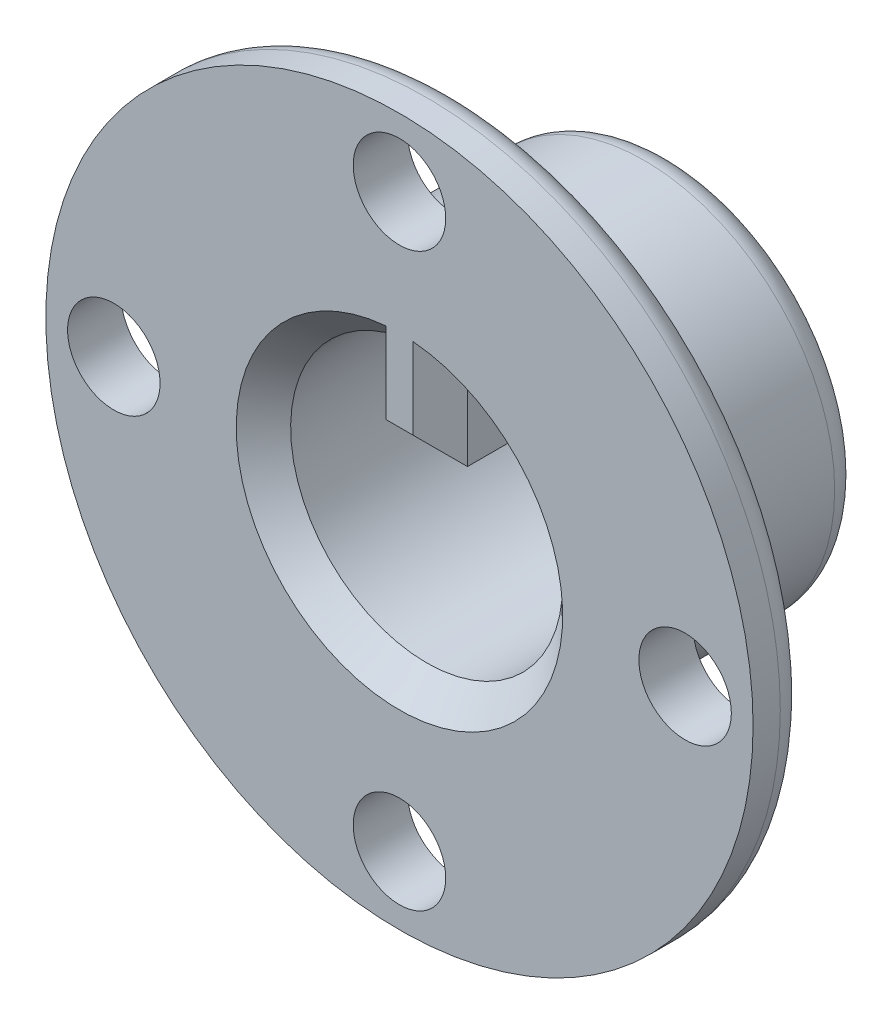
SolidWorks part; units mm, degrees
ref_plane "Alzado" through (0, 0, 0) normal (0, 0, 1) x (1, 0, 0)
ref_plane "Planta" through (0, 0, 0) normal (0, 1, 0) x (1, 0, 0)
ref_plane "Vista lateral" through (0, 0, 0) normal (1, 0, 0) x (0, 0, -1)
sketch "Croquis1" plane through (0, 0, 0) normal (0, 0, 1) x (1, 0, 0)
  line L0 (0, 0) -> (0, 5) construction
  line L2 (-1.5, 5) -> (1.5, 5)
  line L3 (-1.5, 5) -> (-1.5, 2)
  line L4 (-1.5, 2) -> (1.5, 2)
  line L5 (1.5, 5) -> (1.5, 2)
  circle A0 centre (0, 0) radius 5
  circle A1 centre (0, 0) radius 13
  circle A2 centre (0, 0) radius 7
  dimension "D1" = 10
  dimension "D3" = 3
  dimension "D4" = 3
  dimension "D2" = 8
  dimension "D5" = 2
extrude "Saliente-Extruir1" add sketch "Croquis1" against normal blind 10 contours A2 A0 L3 L2 L5 | L0 L4 L5 A0 | L4 L0 A0 L3 | A0 L5 L2 | A0 L2 L3 region at (-0.7402, 3.4628, 0) region at (0.7402, 3.4628, 0) region at (-1.1267, 4.9312, 0) region at (1.1267, 4.9312, 0) region at (-6.802, 0, 0)
extrude "Saliente-Extruir2" add sketch "Croquis1<3>" against normal blind 2 contours A1 A2 region at (-12.6323, 0, 0)
sketch "Croquis1<3>" plane through (0, 0, 0) normal (0, 0, 1) x (1, 0, 0) same geometry as "Croquis1"
hole_wizard "Taladro de margen para M31" positions "Croquis2" profile "Croquis3" hole size "M3" standard "ISO" end condition through all
sketch "Croquis2" plane through (0, 0, 0) normal (0, 0, 1) x (1, 0, 0)
  point P0 (0, 10.5)
  point P11 (10.5, 0)
  point P12 (0, -10.5)
  point P13 (-10.5, 0)
  point P14 (0, 0)
  dimension "D1" = 10.5
  dimension "D2" = 4
sketch "Croquis3" plane through (0, 10.5, 0) normal (1, 0, 0) x (0, -1, 0)
  line L0 (0, 0) -> (0, 10)
  line L1 (0, 10) -> (1.7, 10)
  line L2 (1.7, 10) -> (1.7, 0)
  line L5 (1.7, 0) -> (0, 0)
  line L11 (0, -6.35) -> (0, 107.95) construction
  dimension "Diámetro de taladro hasta el siguiente" = 3.4
  dimension "Profundidad de taladro hasta el siguiente" = 10
chamfer "Chaflán1" distance 1 angle 45 4 edges at (-1.5, 3.3848, -10) (0, 2, -10) (1.5, 3.3848, -10) (0, -5, -10)
fillet "Redondeo2" radius 1 3 edges at (13, 0, -2) (7, 0, -10) (7, 0, -2)
chamfer "Chaflán2" distance 1 angle 45 4 edges at (1.5, 3.3848, 0) (0, 2, 0) (-1.5, 3.3848, 0) (0, -5, 0)
